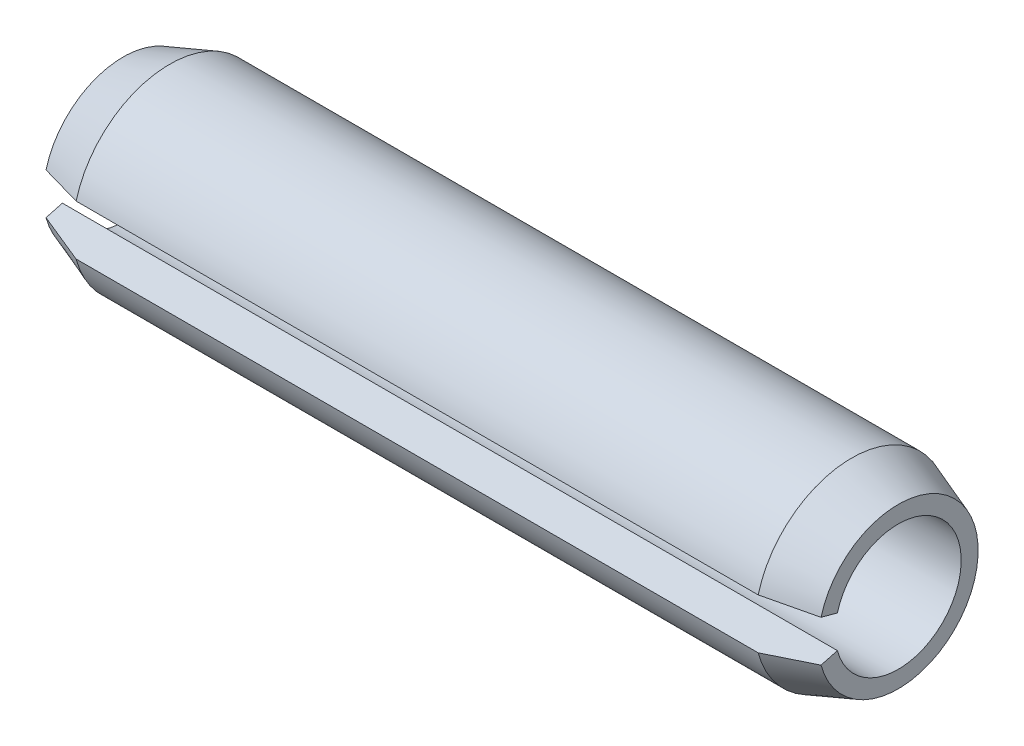
SolidWorks part; units mm, degrees
ref_plane "Front Plane" through (0, 0, 0) normal (0, 0, 1) x (1, 0, 0)
ref_plane "Top Plane" through (0, 0, 0) normal (0, 1, 0) x (1, 0, 0)
ref_plane "Right Plane" through (0, 0, 0) normal (1, 0, 0) x (0, 0, -1)
sketch "BodySke" plane through (0, 0, 0) normal (0, 1, 0) x (1, 0, 0)
  line L0 (0, 0) -> (62.838, 0) construction
  line L1 (0, 0) -> (0, 5) construction
  line L2 (0, 5) -> (40, 5) construction
  line L3 (40, 5) -> (40, 0) construction
  line L4 (0, 3.25) -> (40, 3.25)
  line L5 (0, 4.125) -> (2.4, 5)
  line L6 (20, 5) -> (20, 0) construction
  line L7 (40, 4.125) -> (37.6, 5)
  line L8 (0, 4.125) -> (0, 3.25)
  line L9 (2.4, 5) -> (37.6, 5)
  line L10 (40, 4.125) -> (40, 3.25)
  dimension "D1" = 8.25
  dimension "Pin_dia" = 10
revolve "BaseBody" add sketch "BodySke" angle 360 about L0
sketch "SlitSke" plane through (0, 0, 0) normal (1, 0, 0) x (0, 0, -1)
  line L0 (-6.4036, 0) -> (7.0752, 0) construction
  line L1 (0, -5.7801) -> (0, 6.4996) construction
  line L2 (0, 0) -> (-4.8296, 1.2941)
  line L3 (0, 0) -> (-4.8296, -1.2941)
  circle A0 centre (0, 0) radius 5 construction
  arc A1 (-4.8296, 1.2941) -> (-4.8296, -1.2941) centre (0, 0) ccw
  dimension "Angle" = 15
extrude "Slit" cut sketch "SlitSke" along normal through all
equation "\"D1@BodySke\" =  ( \"Pin_dia@BodySke\" + \"Hole_dia@BodySke\" )  / 2"
